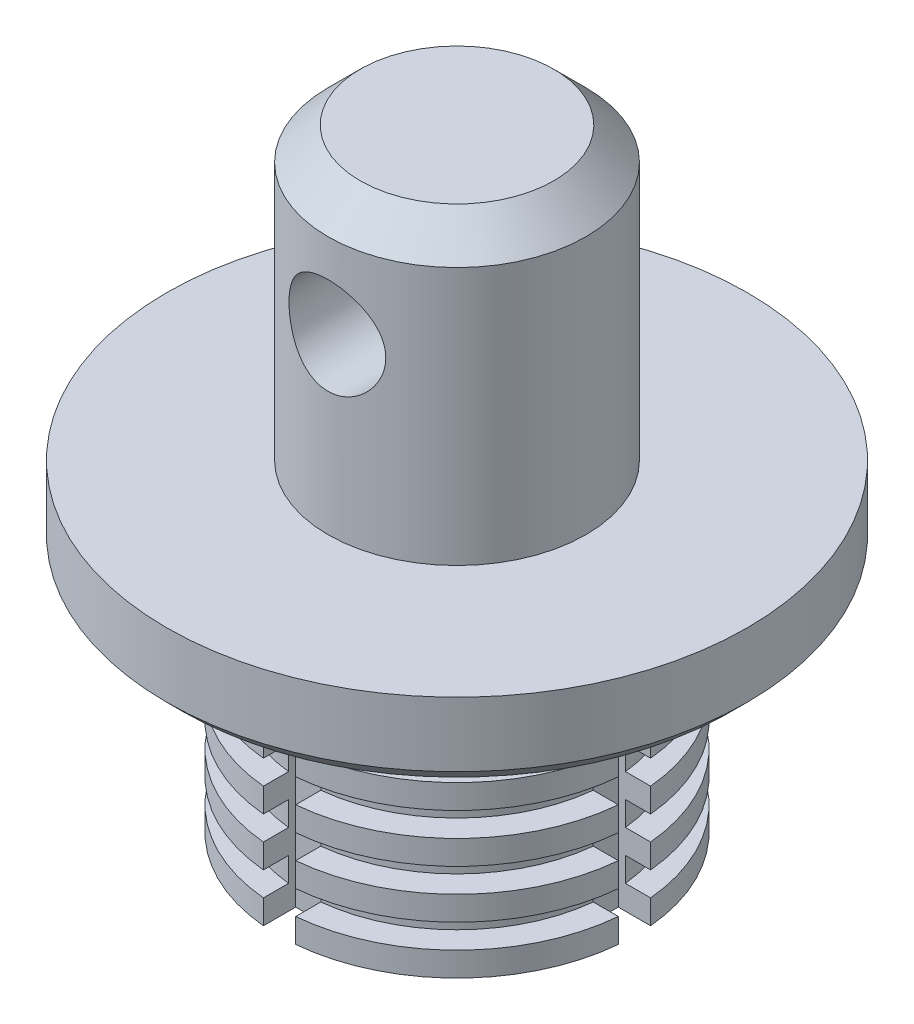
SolidWorks part; units mm, degrees
material "1060 Alloy"
ref_plane "前基準面" through (0, 0, 0) normal (0, 0, 1) x (1, 0, 0)
ref_plane "上基準面" through (0, 0, 0) normal (0, 1, 0) x (1, 0, 0)
ref_plane "右基準面" through (0, 0, 0) normal (1, 0, 0) x (0, 0, -1)
sketch "Sketch1" plane through (0, 0, 0) normal (0, 0, 1) x (1, 0, 0)
  line L0 (0, 0) -> (0, 31.0548) construction
  line L1 (0, 0) -> (11.05, 0)
  line L2 (11.05, 0) -> (11.05, 15)
  line L3 (11.05, 15) -> (18, 15)
  line L4 (18, 15) -> (18, 20)
  line L5 (18, 20) -> (8, 20)
  line L6 (8, 20) -> (8, 38)
  line L7 (8, 38) -> (0, 38)
  line L8 (0, 38) -> (0, 0)
  dimension "D1" = 8
  dimension "D2" = 18
  dimension "D3" = 5
  dimension "D4" = 15
  dimension "D5" = 11.05
  dimension "D6" = 18
revolve "Revolve1" add sketch "Sketch1" angle 360 about L0
sketch "Sketch2" plane through (0, 0, 0) normal (0, 0, 1) x (1, 0, 0)
  line L0 (18, 20) -> (-18, 20) construction
  circle A0 centre (0, 30.7) radius 3
  dimension "D1" = 6
  dimension "D2" = 10.7
extrude "Cut-Extrude1" cut sketch "Sketch2" against normal through all both and the other way through all contours A0
chamfer "Chamfer1" distance 1 angle 45 1 edges at (0, 15, -18)
ref_axis "Axis1" through (0, -2, 0) along (0, 1, 0)
sketch "Sketch3" plane through (0, 0, 0) normal (0, 0, 1) x (1, 0, 0)
  line L0 (11.05, 0) -> (11.05, 15) construction
  line L1 (11.05, 1.5) -> (9.5, 1.5)
  line L2 (11.05, 1.5) -> (11.05, 3)
  line L3 (11.05, 3) -> (9.5, 3)
  line L4 (9.5, 1.5) -> (9.5, 3)
  line L5 (19.8, 0) -> (-19.8, 0) construction
  line L6 (11.05, 4.5) -> (9.5, 4.5)
  line L7 (11.05, 4.5) -> (11.05, 6)
  line L8 (11.05, 6) -> (9.5, 6)
  line L9 (9.5, 4.5) -> (9.5, 6)
  line L10 (11.05, 7.5) -> (9.5, 7.5)
  line L11 (11.05, 7.5) -> (11.05, 9)
  line L12 (11.05, 9) -> (9.5, 9)
  line L13 (9.5, 7.5) -> (9.5, 9)
  line L14 (11.05, 10.5) -> (9.5, 10.5)
  line L15 (11.05, 10.5) -> (11.05, 12)
  line L16 (11.05, 12) -> (9.5, 12)
  line L17 (9.5, 10.5) -> (9.5, 12)
  line L18 (11.05, 13.5) -> (9.5, 13.5)
  line L19 (11.05, 13.5) -> (11.05, 15)
  line L20 (11.05, 15) -> (9.5, 15)
  line L21 (9.5, 13.5) -> (9.5, 15)
  dimension "D1" = 1.5
  dimension "D2" = 1.5
  dimension "D3" = 1.5
  dimension "D4" = 1.5
  dimension "D5" = 1.5
  dimension "D6" = 1.5
  dimension "D7" = 1.5
  dimension "D8" = 1.55
revolve "Cut-Revolve1" cut sketch "Sketch3" angle 360 about axis through (0, -2, 0) along (0, 1, 0)
sketch "Sketch4" plane through (0, 15, 0) normal (0, -1, 0) x (1, 0, 0)
  circle A0 centre (0, 0) radius 11.05
  circle A1 centre (0, 0) radius 14.7
  dimension "D1" = 22.1
  dimension "D2" = 29.4
extrude "Cut-Extrude3" cut sketch "Sketch4" against normal blind 1
sketch "Sketch5" plane through (0, 0, 0) normal (0, -1, 0) x (1, 0, 0)
  line L0 (0, 0) -> (-18, 0) construction
  line L1 (-1, -12) -> (1, -12)
  line L2 (-1, -12) -> (-1, -9)
  line L3 (-1, -9) -> (1, -9)
  line L4 (1, -12) -> (1, -9)
  line L5 (-1, 9) -> (1, 9)
  line L6 (-1, 9) -> (-1, 12)
  line L7 (-1, 12) -> (1, 12)
  line L8 (1, 9) -> (1, 12)
  line L9 (-12, -1) -> (-9, -1)
  line L10 (-12, -1) -> (-12, 1)
  line L11 (-12, 1) -> (-9, 1)
  line L12 (-9, -1) -> (-9, 1)
  line L13 (9, -1) -> (12, -1)
  line L14 (9, -1) -> (9, 1)
  line L15 (9, 1) -> (12, 1)
  line L16 (12, -1) -> (12, 1)
  line L17 (0, 0) -> (0, 18) construction
  circle A0 centre (0, 0) radius 18 construction
  point P22 (0, 9)
  point P24 (-9, 0)
  dimension "D1" = 9
  dimension "D2" = 9
  dimension "D3" = 9
  dimension "D4" = 9
  dimension "D5" = 3
  dimension "D6" = 2
  dimension "D7" = 2
extrude "Cut-Extrude4" cut sketch "Sketch5" against normal blind 15
fillet "Fillet1" radius 1 8 edges at (9.2236, 15, -1) (9.2236, 15, 1) (-1, 15, -9.2236) (1, 15, -9.2236) (-9.2236, 15, 1) (-9.2236, 15, -1) (1, 15, 9.2236) (-1, 15, 9.2236)
chamfer "Chamfer2" distance 2 angle 45 1 edges at (0, 38, -8)
